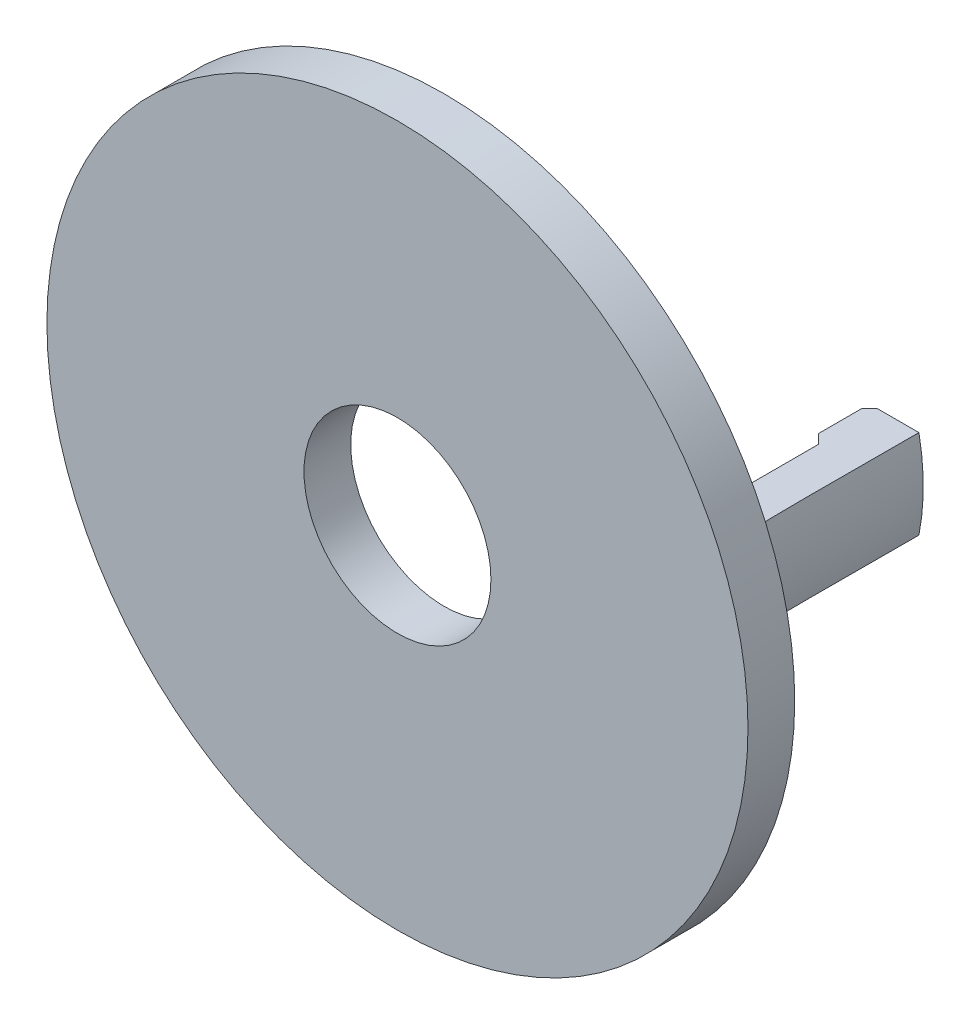
SolidWorks part; units mm, degrees
ref_plane "Front" through (0, 0, 0) normal (0, 0, 1) x (1, 0, 0)
ref_plane "Top" through (0, 0, 0) normal (0, 1, 0) x (1, 0, 0)
ref_plane "Right" through (0, 0, 0) normal (1, 0, 0) x (0, 0, -1)
sketch "Guard base sketch" plane through (0, 0, 0) normal (0, 0, 1) x (1, 0, 0)
  circle A0 centre (0, 0) radius 37.5
  dimension "D1" = 75
extrude "Guard" add sketch "Guard base sketch" along normal blind 5
sketch "Inner axle base sketch" plane through (0, 0, 5) normal (0, 0, 1) x (1, 0, 0)
  circle A0 centre (0, 0) radius 10
  dimension "D1" = 20
extrude "Inner axle hole" cut sketch "Inner axle base sketch" against normal through all
sketch "Coupling tooth base sketch" plane through (0, 0, 0) normal (0, 1, 0) x (1, 0, 0)
  line L0 (19.5, 0) -> (26, 0) construction
  line L1 (26, 0) -> (26, 27) construction
  line L2 (26, 0) -> (16.5, 0)
  line L3 (26, 27) -> (19.5, 27) construction
  line L4 (19.5, 27) -> (18, 25.5) construction
  line L5 (18, 21) -> (19.5, 19.5) construction
  line L6 (19.5, 19.5) -> (19.5, 0) construction
  line L7 (19.75, 20.3107) -> (19.75, 2.8964)
  line L8 (19.5, 3) -> (16.5, 0) construction
  line L9 (19.75, 20.3107) -> (18.75, 21.3107)
  line L10 (18, 25.5) -> (18, 21) construction
  line L11 (18.75, 21.3107) -> (18.75, 25.8964)
  line L12 (26, 0) -> (26, 26.75)
  line L13 (10, 0) -> (-10, 0) construction
  line L14 (19.75, 2.8964) -> (16.8536, 0)
  line L15 (18.75, 25.8964) -> (19.6036, 26.75)
  line L16 (19.6036, 26.75) -> (26, 26.75)
  line L17 (24.5, 26.5113) -> (24.5, 41.0721) construction
  line L18 (24.5, 12.4795) -> (24.5, 18.7128) construction
  line L19 (26, 0) -> (37.5, 0)
  line L20 (37.5, 0) -> (37.5, 26.75)
  line L21 (37.5, 26.75) -> (26, 26.75)
  spline S0 degree 3 poles (24.5, 26.75) (24.5, 22.7282) (24.4901, 20.5425) (24.5119, 14.9424) (24.2749, 4.9839) (26, 0) knots 0 0 0 0 0.446605 0.546605 1 1 1 1
  dimension "D1" = 135
  dimension "D2" = 9.5
  dimension "D3" = 8
  dimension "D4" = 27
  dimension "D5" = 7.5
  dimension "D6" = 0.25
  dimension "D7" = 0.25
  dimension "D8" = 0.25
  dimension "D9" = 0.75
  dimension "D10" = 1.5
  dimension "D11" = 225
  dimension "D12" = 0.25
  dimension "D13" = 1.5
  dimension "D14" = 0.75
  dimension "D15" = 26
extrude "Coupling tooth" add sketch "Coupling tooth base sketch" along normal blind 4.75 and the other way blind 4.75 contours S0 L16 L15 L11 L9 L7 L14 L2 region at (22.0194, 0, -13.0102)
ref_axis "Center Z" through (0, 0, 0) along (0, 0, -1)
revolve "Circularity cut" cut sketch "Sketch6<4>" angle 360 about axis through (0, 0, 0) along (0, 0, -1) region at (25.2982, 0, -14.9997) region at (31.75, 0, -13.375)
sketch "Sketch6<4>" plane through (0, 0, 0) normal (0, 1, 0) x (1, 0, 0) same geometry as "Coupling tooth base sketch"
mirror "Coupling teeth" about plane through (0, 0, 0) normal (1, 0, 0) of "Coupling tooth", "Circularity cut"
equation "\"mate_room\"= 0.25"
equation "\"D6@Coupling tooth base sketch\"=\"mate_room\""
equation "\"D8@Coupling tooth base sketch\"=\"mate_room\""
equation "\"D7@Coupling tooth base sketch\"=\"mate_room\""
equation "\"removal_room\"= 0.75"
equation "\"D9@Coupling tooth base sketch\"=\"removal_room\""
equation "\"D12@Coupling tooth base sketch\"=\"mate_room\""
equation "\"D14@Coupling tooth base sketch\"=\"removal_room\""
equation "\"small_inner_axle_diameter\"=17"
equation "\"D1@Inner axle base sketch\" = \"large_inner_axle_diameter\""
equation "\"large_inner_axle_diameter\"=20"
equation "\"guard_thickness\"=5"
equation "\"spool_inner_diameter_room\"=1"
equation "\"53_55_spool_inner_diameter\"=53"
equation "\"53_55_spool_thickness\"=55"
equation "\"53_55_guard_diameter\"=75"
equation "\"53_55_coupling_tooth_height\"=27"
equation "\"53_55_coupling_tooth_thickness_total\"=8"
equation "\"53_55_coupling_tooth_protrusion\"=1.5"
equation "\"53_55_coupling_tooth_head_height\"=7.5"
equation "\"53_55_coupling_tooth_depth\"=10"
equation "\"D1@Guard base sketch\"=\"53_55_guard_diameter\""
equation "\"D1@Guard\"=\"guard_thickness\""
equation "\"D4@Coupling tooth base sketch\"=\"53_55_coupling_tooth_height\""
equation "\"53_55_coupling_tooth_base_thickness\"=9.5"
equation "\"D2@Coupling tooth base sketch\"=\"53_55_coupling_tooth_base_thickness\""
equation "\"D3@Coupling tooth base sketch\"=\"53_55_coupling_tooth_thickness_total\""
equation "\"D5@Coupling tooth base sketch\"=\"53_55_coupling_tooth_head_height\""
equation "\"D10@Coupling tooth base sketch\"=\"53_55_coupling_tooth_protrusion\""
equation "\"D1@Coupling tooth\"=\"53_55_coupling_tooth_depth\"/2 - \"mate_room\""
equation "\"D2@Coupling tooth\"=\"53_55_coupling_tooth_depth\"/2 - \"mate_room\""
equation "\"D15@Coupling tooth base sketch\"=(\"53_55_spool_inner_diameter\" - \"spool_inner_diameter_room\")/2"
